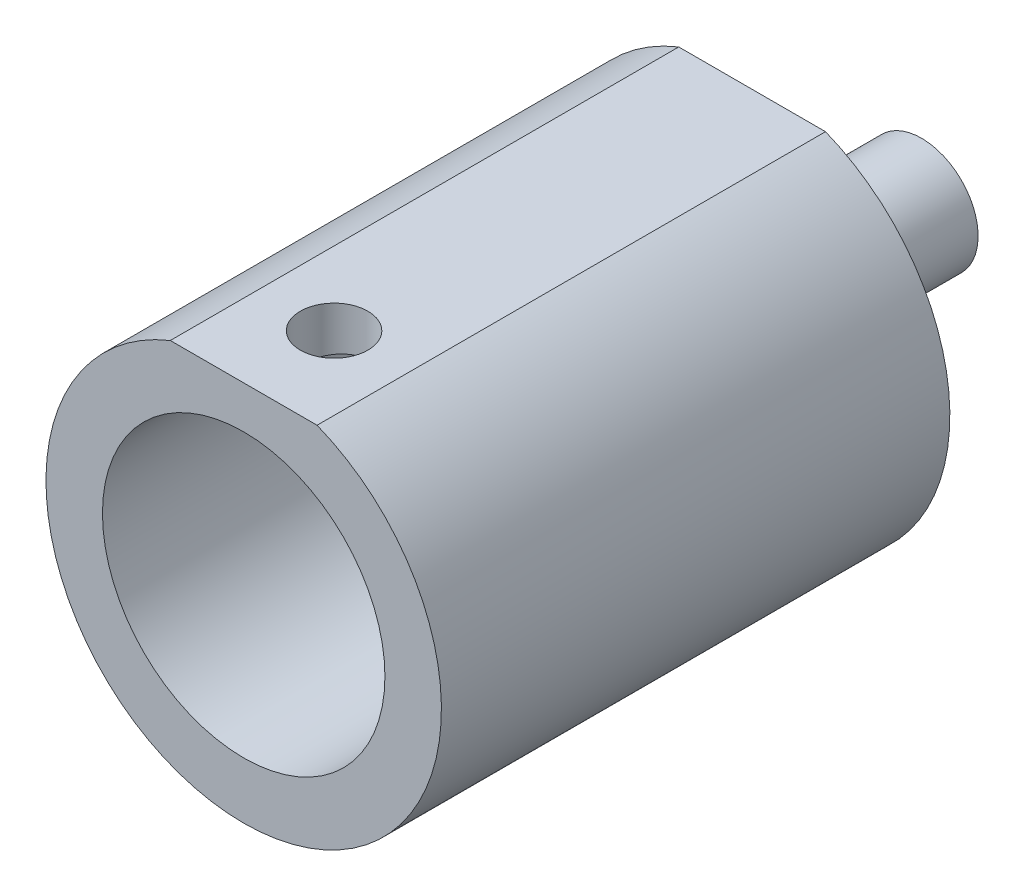
SolidWorks part; units mm, degrees
ref_plane "Front Plane" through (0, 0, 0) normal (0, 0, 1) x (1, 0, 0)
ref_plane "Top Plane" through (0, 0, 0) normal (0, 1, 0) x (1, 0, 0)
ref_plane "Right Plane" through (0, 0, 0) normal (1, 0, 0) x (0, 0, -1)
sketch "Sketch1" plane through (0, 0, 0) normal (0, 1, 0) x (1, 0, 0)
  line L6 (0, 0) -> (7.9375, 0) construction
  line L7 (7.9375, 0) -> (11.1125, 0)
  line L8 (11.1125, 0) -> (11.1125, 28.575)
  line L9 (11.1125, 28.575) -> (3.175, 28.575)
  line L10 (3.175, 28.575) -> (3.175, 38.1)
  line L11 (3.175, 38.1) -> (0, 38.1)
  line L12 (0, 38.1) -> (0, 25.4)
  line L13 (0, 25.4) -> (0, 0) construction
  line L14 (0, 25.4) -> (7.9375, 25.4)
  line L15 (7.9375, 25.4) -> (7.9375, 0)
  dimension "D1" = 3.175
  dimension "D2" = 7.9375
  dimension "D3" = 3.175
  dimension "D4" = 25.4
  dimension "D5" = 9.525
revolve "Revolve1" add sketch "Sketch1" angle 360 about L13
sketch "Sketch3" plane through (0, 0, 0) normal (1, 0, 0) x (0, 0, -1)
  line L0 (0, 10.3188) -> (0, 11.1125)
  line L1 (0, 11.1125) -> (0, -11.1125) construction
  line L2 (0, 11.1125) -> (28.575, 11.1125)
  line L3 (28.575, 11.1125) -> (28.575, 10.3188)
  line L4 (28.575, -11.1125) -> (28.575, 11.1125) construction
  line L5 (28.575, 10.3188) -> (0, 10.3188)
  dimension "D1" = 0.7937
extrude "Cut-Extrude1" cut sketch "Sketch3" against normal through all both and the other way through all
hole_wizard "#6 Clearance Hole1" positions "Sketch4" profile "Sketch5" hole size "#6" standard "ANSI Inch" end condition up to next
sketch "Sketch4" plane through (0, 10.3188, 0) normal (0, 1, 0) x (1, 0, 0)
  line L0 (-7.9375, 25.4) -> (7.9375, 25.4) construction
  point P0 (0, 5.08)
  point P5 (0, 0)
  dimension "D1" = 20.32
sketch "Sketch5" plane through (0, 10.3188, -5.08) normal (1, 0, 0) x (0, 0, 1)
  line L0 (0, 0) -> (0, 2.3813)
  line L1 (0, 2.3813) -> (1.8986, 2.3813)
  line L2 (1.8986, 2.3813) -> (1.8986, 0)
  line L5 (1.8986, 0) -> (0, 0)
  line L11 (0, -6.35) -> (0, 107.95) construction
  dimension "Thru Hole Dia." = 3.7973
  dimension "Thru Hole Depth" = 2.3813
